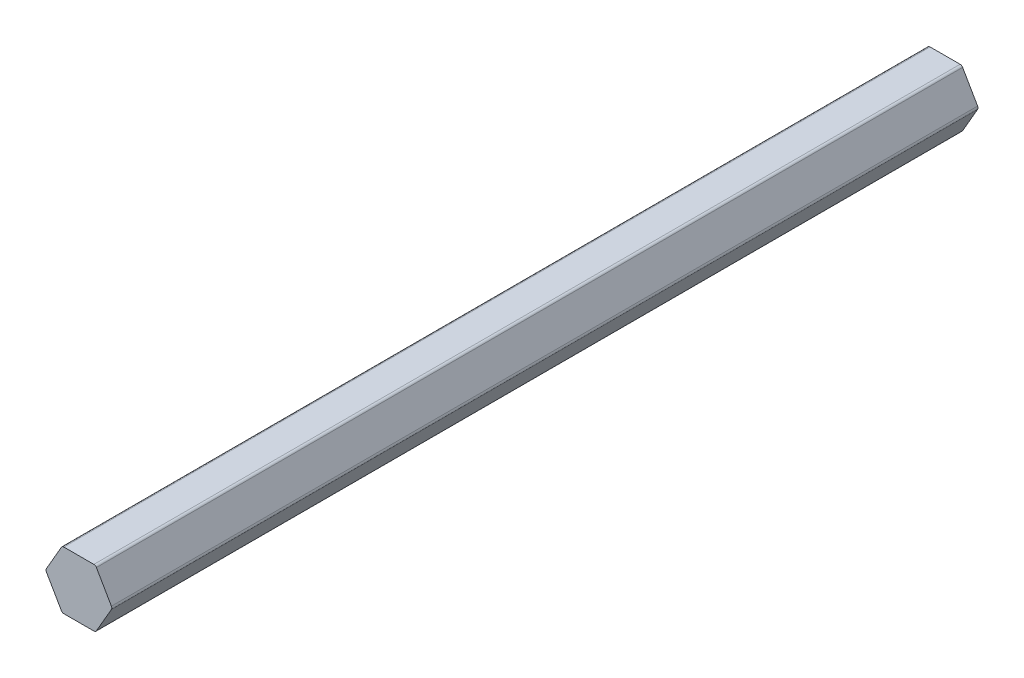
SolidWorks part; units mm, degrees
material "AISI 1020 Steel, Cold Rolled"
ref_plane "Front Plane" through (0, 0, 0) normal (0, 0, 1) x (1, 0, 0)
ref_plane "Top Plane" through (0, 0, 0) normal (0, 1, 0) x (1, 0, 0)
ref_plane "Right Plane" through (0, 0, 0) normal (1, 0, 0) x (0, 0, -1)
other "Configuration Table"
sketch "Sketch1" plane through (0, 0, 0) normal (0, 0, 1) x (1, 0, 0)
  line L1 (7.3323, 0) -> (3.6662, 6.35)
  line L2 (3.6662, 6.35) -> (-3.6662, 6.35)
  line L3 (-3.6662, 6.35) -> (-7.3323, 0)
  line L4 (-7.3323, 0) -> (-3.6662, -6.35)
  line L5 (-3.6662, -6.35) -> (3.6662, -6.35)
  line L6 (3.6662, -6.35) -> (7.3323, 0)
  circle A0 centre (0, 0) radius 6.35 construction
  dimension "D1" = 12.7
extrude "Boss-Extrude1" add sketch "Sketch1" along normal mid plane 190.5
fillet "Fillet1" radius 0.635 6 edges at (3.6662, -6.35, 0) (-3.6662, -6.35, 0) (-7.3323, 0, 0) (-3.6662, 6.35, 0) (7.3323, 0, 0) (3.6662, 6.35, 0)
equation "\"length\"= 7.5"
equation "\"D1@Boss-Extrude1\"=\"length\""
